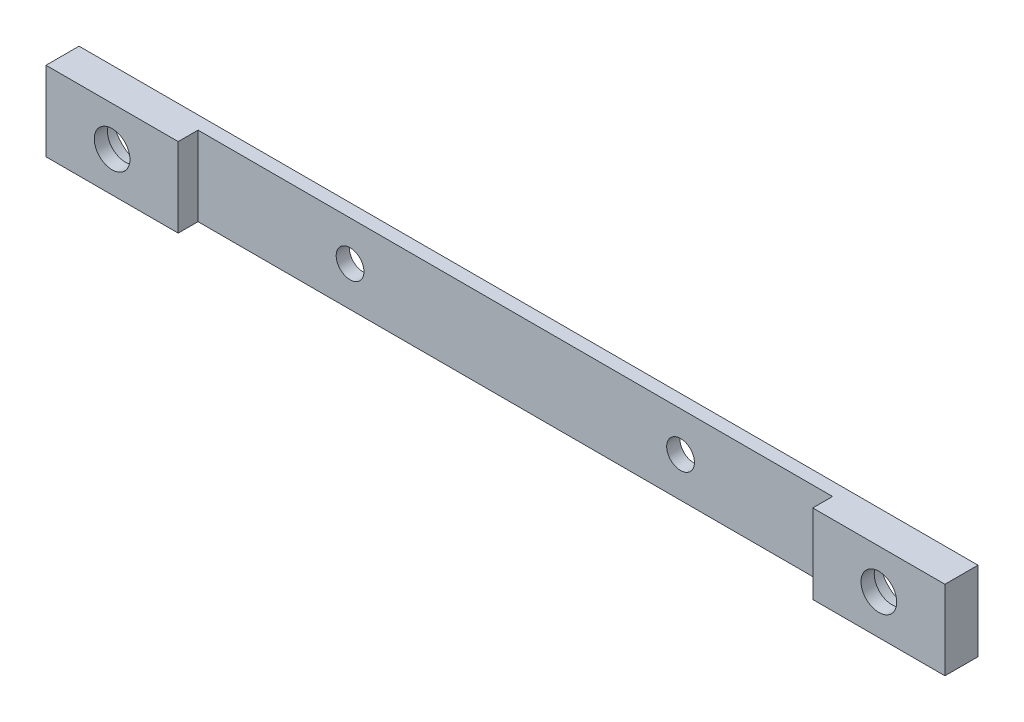
SolidWorks part; units mm, degrees
material "ABS"
ref_plane "Front Plane" through (0, 0, 0) normal (0, 0, 1) x (1, 0, 0)
ref_plane "Top Plane" through (0, 0, 0) normal (0, 1, 0) x (1, 0, 0)
ref_plane "Right Plane" through (0, 0, 0) normal (1, 0, 0) x (0, 0, -1)
sketch "Sketch1" plane through (0, 0, 0) normal (0, 0, 1) x (1, 0, 0)
  line L0 (-68, -6) -> (68, -6)
  line L1 (-68, -6) -> (-68, 6)
  line L2 (68, -6) -> (68, 6)
  line L3 (-68, 6) -> (68, 6)
  line L4 (-68, -6) -> (68, 6) construction
  line L5 (68, -6) -> (-68, 6) construction
  line L6 (-68, 0) -> (68, 0) construction
  line L7 (0, 6) -> (0, -6) construction
  circle A0 centre (-58, 0) radius 2.7
  circle A1 centre (-25, 0) radius 2.1
  circle A2 centre (-58, 0) radius 5
  circle A3 centre (25, 0) radius 2.1
  circle A4 centre (58, 0) radius 5
  circle A5 centre (58, 0) radius 2.7
  point P1 (0, 0)
  dimension "D3" = 4.2
  dimension "D4" = 5.4
  dimension "D5" = 10
  dimension "D6" = 10
  dimension "D7" = 50
  dimension "D1" = 12
  dimension "D2" = 136
extrude "Boss-Extrude1" add sketch "Sketch1" along normal blind 5 contours L3 L1 L0 L2 A3 A2 A1 A4 | A2 A0 | A4 A5 region at (0, 0, 0) region at (-62.8586, 0, 0) region at (53.1414, 0, 0)
sketch "Sketch2" plane through (0, -6, 0) normal (0, -1, 0) x (1, 0, 0)
  line L0 (-68, 5) -> (68, 5) construction
  line L1 (-48, 5) -> (48, 5)
  line L2 (-48, 5) -> (-48, 2)
  line L3 (-48, 2) -> (48, 2)
  line L4 (48, 5) -> (48, 2)
  line L5 (0, 0) -> (0, 5) construction
  line L6 (-68, 0) -> (68, 0) construction
  point P10 (0, 2)
  dimension "D1" = 3
  dimension "D2" = 96
extrude "Cut-Extrude1" cut sketch "Sketch2" against normal up to surface (12 mm away) up to face at (0, 6, 2.5)
extrude "Cut-Extrude2" cut sketch "Sketch1<3>" along normal blind 3 contours A2 | A4
sketch "Sketch1<3>" plane through (0, 0, 0) normal (0, 0, 1) x (1, 0, 0) same geometry as "Sketch1"
